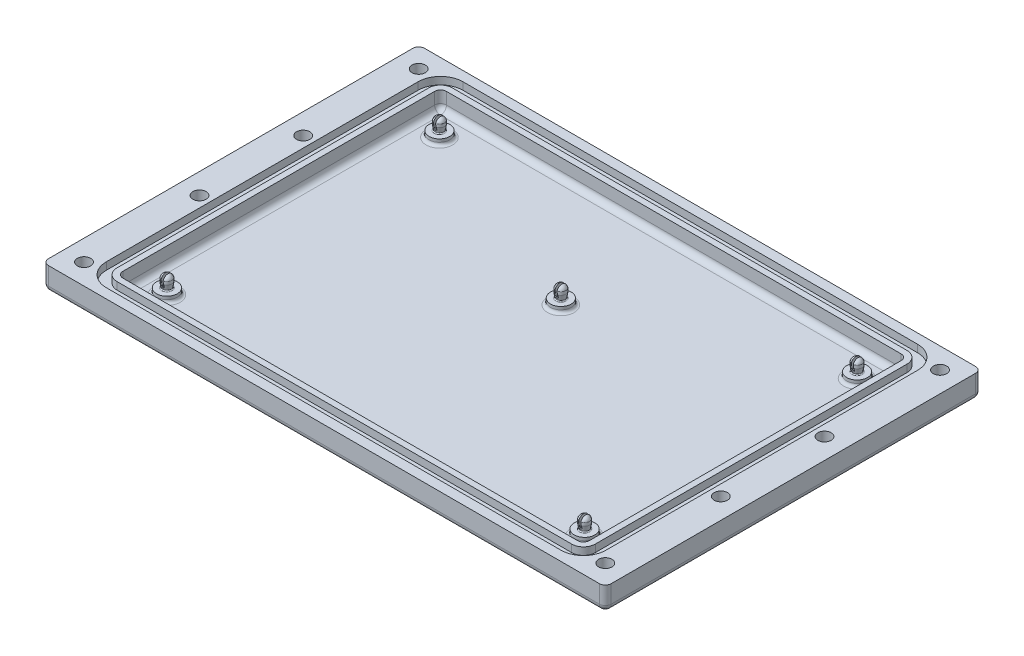
SolidWorks part; units mm, degrees
ref_plane "Front Plane" through (0, 0, 0) normal (0, 0, 1) x (1, 0, 0)
ref_plane "Top Plane" through (0, 0, 0) normal (0, 1, 0) x (1, 0, 0)
ref_plane "Right Plane" through (0, 0, 0) normal (1, 0, 0) x (0, 0, -1)
sketch "Sketch1" plane through (0, 0, 0) normal (0, 1, 0) x (1, 0, 0)
  line L1 (0, 0) -> (190, 0)
  line L2 (0, 0) -> (0, 127)
  line L3 (0, 127) -> (190, 127)
  line L4 (190, 0) -> (190, 127)
  dimension "D1" = 127
  dimension "D2" = 190
extrude "Boss-Extrude1" add sketch "Sketch1" along normal blind 8
fillet "Fillet1" radius 2 8 edges at (190, 0, -63.5) (95, 0, 0) (0, 0, -63.5) (95, 0, -127) (190, 4, -127) (0, 4, -127) (190, 4, 0) (0, 4, 0)
sketch "Sketch2" plane through (0, 8, 0) normal (0, 1, 0) x (1, 0, 0)
  line L0 (95, 127) -> (95, 0) construction
  line L1 (16.26, 8.89) -> (173.74, 8.89)
  line L2 (16.26, 8.89) -> (16.26, 118.11)
  line L3 (16.26, 118.11) -> (173.74, 118.11)
  line L4 (173.74, 8.89) -> (173.74, 118.11)
  line L5 (16.26, 8.89) -> (173.74, 118.11) construction
  line L6 (16.26, 118.11) -> (173.74, 8.89) construction
  line L7 (188, 127) -> (2, 127) construction
  line L8 (2, 0) -> (188, 0) construction
  point P0 (95, 63.5)
  point P11 (95, 63.5)
  dimension "D1" = 109.22
  dimension "D2" = 157.48
extrude "Cut-Extrude1" cut sketch "Sketch2" against normal blind 6
fillet "Fillet2" radius 2 8 edges at (95, 2, -118.11) (173.74, 2, -63.5) (95, 2, -8.89) (16.26, 2, -63.5) (16.26, 5, -8.89) (173.74, 5, -8.89) (173.74, 5, -118.11) (16.26, 5, -118.11)
sketch "Sketch3" plane through (0, 8, 0) normal (0, 1, 0) x (1, 0, 0)
  line L0 (18.26, 5.39) -> (171.74, 5.39) construction
  line L1 (177.24, 10.89) -> (177.24, 116.11) construction
  line L2 (171.74, 121.61) -> (18.26, 121.61) construction
  line L3 (12.76, 116.11) -> (12.76, 10.89) construction
  line L4 (171.74, 123.71) -> (18.26, 123.71)
  line L5 (10.66, 116.11) -> (10.66, 10.89)
  line L6 (18.26, 3.29) -> (171.74, 3.29)
  line L7 (179.34, 10.89) -> (179.34, 116.11)
  line L8 (175.74, 10.89) -> (175.74, 116.11)
  line L9 (18.26, 6.89) -> (171.74, 6.89)
  line L10 (14.26, 116.11) -> (14.26, 10.89)
  line L11 (171.74, 120.11) -> (18.26, 120.11)
  line L12 (175.74, 10.89) -> (175.74, 116.11)
  line L13 (18.26, 6.89) -> (171.74, 6.89)
  line L14 (14.26, 116.11) -> (14.26, 10.89)
  line L15 (171.74, 120.11) -> (18.26, 120.11)
  arc A0 (171.74, 5.39) -> (177.24, 10.89) centre (171.74, 10.89) ccw construction
  arc A1 (177.24, 116.11) -> (171.74, 121.61) centre (171.74, 116.11) ccw construction
  arc A2 (18.26, 121.61) -> (12.76, 116.11) centre (18.26, 116.11) ccw construction
  arc A3 (12.76, 10.89) -> (18.26, 5.39) centre (18.26, 10.89) ccw construction
  arc A4 (18.26, 123.71) -> (10.66, 116.11) centre (18.26, 116.11) ccw
  arc A5 (10.66, 10.89) -> (18.26, 3.29) centre (18.26, 10.89) ccw
  arc A6 (171.74, 3.29) -> (179.34, 10.89) centre (171.74, 10.89) ccw
  arc A7 (179.34, 116.11) -> (171.74, 123.71) centre (171.74, 116.11) ccw
  arc A8 (175.74, 116.11) -> (171.74, 120.11) centre (171.74, 116.11) ccw
  arc A9 (171.74, 6.89) -> (175.74, 10.89) centre (171.74, 10.89) ccw
  arc A10 (14.26, 10.89) -> (18.26, 6.89) centre (18.26, 10.89) ccw
  arc A11 (18.26, 120.11) -> (14.26, 116.11) centre (18.26, 116.11) ccw
  arc A12 (175.74, 116.11) -> (171.74, 120.11) centre (171.74, 116.11) ccw
  arc A13 (171.74, 6.89) -> (175.74, 10.89) centre (171.74, 10.89) ccw
  arc A14 (14.26, 10.89) -> (18.26, 6.89) centre (18.26, 10.89) ccw
  arc A15 (18.26, 120.11) -> (14.26, 116.11) centre (18.26, 116.11) ccw
  dimension "D1" = 2
  dimension "D2" = 3.6
  dimension "D3" = 1.5
extrude "Cut-Extrude2" cut sketch "Sketch3" against normal blind 2.5
sketch "Sketch4" plane through (0, 2, 0) normal (0, 1, 0) x (1, 0, 0)
  circle A0 centre (24.5, 109.5) radius 3.5
  circle A1 centre (94, 81) radius 3.5
  circle A2 centre (165.5, 109.5) radius 3.5
  circle A3 centre (165.5, 17.5) radius 3.5
  circle A4 centre (24.5, 17.5) radius 3.5
  circle A5 centre (24.5, 109.5) radius 1.6 construction
  dimension "D1" = 7
extrude "Boss-Extrude2" add sketch "Sketch4" along normal blind 2
fillet "Fillet3" radius 1 5 edges at (165.5, 2, -113) (165.5, 2, -21) (24.5, 2, -21) (94, 2, -84.5) (24.5, 2, -113)
sketch "Sketch7" plane through (0, 4, 0) normal (0, 1, 0) x (1, 0, 0)
  circle A0 centre (24.5, 109.5) radius 1.4
  circle A1 centre (94, 81) radius 1.4
  circle A2 centre (165.5, 109.5) radius 1.4
  circle A3 centre (165.5, 17.5) radius 1.4
  circle A4 centre (24.5, 17.5) radius 1.4
  dimension "D1" = 2.8
extrude "Boss-Extrude3" add sketch "Sketch7" along normal blind 2 draft 9 draft outward yes
sketch "Sketch8" plane through (0, 6, 0) normal (0, 1, 0) x (1, 0, 0)
  circle A0 centre (165.5, 109.5) radius 1.7168 construction
  circle A1 centre (94, 81) radius 1.7168 construction
  circle A2 centre (24.5, 109.5) radius 1.7168 construction
  circle A3 centre (24.5, 17.5) radius 1.7168 construction
  circle A4 centre (165.5, 17.5) radius 1.7168 construction
  circle A5 centre (165.5, 109.5) radius 1.7168
  circle A6 centre (94, 81) radius 1.7168
  circle A7 centre (24.5, 109.5) radius 1.7168
  circle A8 centre (24.5, 17.5) radius 1.7168
  circle A9 centre (165.5, 17.5) radius 1.7168
extrude "Boss-Extrude4" add sketch "Sketch8" along normal blind 1 draft 3
dome "Dome2" faces to dome 1 distance 1.3 reverse direction no elliptical dome no face at (165.5, 7, -15.8356) parameters "D1"=1.3
dome "Dome3" faces to dome 1 distance 1.3 reverse direction no elliptical dome no face at (165.5, 7, -107.8356) parameters "D1"=1.3
dome "Dome4" faces to dome 1 distance 1.3 reverse direction no elliptical dome no face at (94, 7, -79.3356) parameters "D1"=1.3
dome "Dome5" faces to dome 1 distance 1.3 reverse direction no elliptical dome no face at (24.5, 7, -15.8356) parameters "D1"=1.3
dome "Dome6" faces to dome 1 distance 1.3 reverse direction no elliptical dome no face at (24.5, 7, -107.8356) parameters "D1"=1.3
sketch "Sketch9" plane through (0, 8, 0) normal (0, 1, 0) x (1, 0, 0)
  line L1 (165.85, 14.5) -> (165.15, 14.5)
  line L2 (165.85, 14.5) -> (165.85, 20.5)
  line L3 (165.85, 20.5) -> (165.15, 20.5)
  line L4 (165.15, 14.5) -> (165.15, 20.5)
  line L5 (165.85, 14.5) -> (165.15, 20.5) construction
  line L6 (165.85, 20.5) -> (165.15, 14.5) construction
  line L7 (165.85, 106.5) -> (165.15, 106.5)
  line L8 (165.85, 106.5) -> (165.85, 112.5)
  line L9 (165.85, 112.5) -> (165.15, 112.5)
  line L10 (165.15, 106.5) -> (165.15, 112.5)
  line L11 (165.85, 106.5) -> (165.15, 112.5) construction
  line L12 (165.85, 112.5) -> (165.15, 106.5) construction
  line L13 (94.35, 78) -> (93.65, 78)
  line L14 (94.35, 78) -> (94.35, 84)
  line L15 (94.35, 84) -> (93.65, 84)
  line L16 (93.65, 78) -> (93.65, 84)
  line L17 (94.35, 78) -> (93.65, 84) construction
  line L18 (94.35, 84) -> (93.65, 78) construction
  line L19 (24.85, 106.5) -> (24.15, 106.5)
  line L20 (24.85, 106.5) -> (24.85, 112.5)
  line L21 (24.85, 112.5) -> (24.15, 112.5)
  line L22 (24.15, 106.5) -> (24.15, 112.5)
  line L23 (24.85, 106.5) -> (24.15, 112.5) construction
  line L24 (24.85, 112.5) -> (24.15, 106.5) construction
  line L25 (24.85, 14.5) -> (24.15, 14.5)
  line L26 (24.85, 14.5) -> (24.85, 20.5)
  line L27 (24.85, 20.5) -> (24.15, 20.5)
  line L28 (24.15, 14.5) -> (24.15, 20.5)
  line L29 (24.85, 14.5) -> (24.15, 20.5) construction
  line L30 (24.85, 20.5) -> (24.15, 14.5) construction
  point P0 (165.5, 17.5)
  point P6 (165.5, 109.5)
  point P12 (94, 81)
  point P18 (24.5, 109.5)
  point P24 (24.5, 17.5)
  dimension "D1" = 6
  dimension "D2" = 0.7
extrude "Cut-Extrude3" cut sketch "Sketch9" against normal offset from surface 1 and the other way through all up to face at (24.5, 4, -14)
fillet "Fillet4" radius 0.2 40 edges at (165.85, 5, -17.5) (165.5, 5, -15.9416) (165.15, 5, -17.5) (165.5, 5, -19.0584) (165.85, 5, -109.5) (165.5, 5, -107.9416) (165.15, 5, -109.5) (165.5, 5, -111.0584) (94.35, 5, -81) (94, 5, -79.4416) (93.65, 5, -81) (94, 5, -82.5584) (24.85, 5, -17.5) (24.5, 5, -15.9416) (24.15, 5, -17.5) (24.5, 5, -19.0584) (24.85, 5, -109.5) (24.5, 5, -107.9416) (24.15, 5, -109.5) (24.5, 5, -111.0584)
fillet "Fillet5" radius 0.3 5 edges at (165.5, 4, -16.1) (165.5, 4, -108.1) (94, 4, -79.6) (24.5, 4, -16.1) (24.5, 4, -108.1)
sketch "Sketch10" plane through (0, 8, 0) normal (0, 1, 0) x (1, 0, 0)
  circle A0 centre (7, 120) radius 2.25 construction
  circle A1 centre (7, 81) radius 2.25 construction
  circle A2 centre (7, 46) radius 2.25 construction
  circle A3 centre (7, 7) radius 2.25 construction
  circle A4 centre (183, 7) radius 2.25 construction
  circle A5 centre (183, 46) radius 2.25 construction
  circle A6 centre (183, 81) radius 2.25 construction
  circle A7 centre (183, 120) radius 2.25 construction
  circle A8 centre (7, 120) radius 2.25
  circle A9 centre (7, 81) radius 2.25
  circle A10 centre (7, 46) radius 2.25
  circle A11 centre (7, 7) radius 2.25
  circle A12 centre (183, 7) radius 2.25
  circle A13 centre (183, 46) radius 2.25
  circle A14 centre (183, 81) radius 2.25
  circle A15 centre (183, 120) radius 2.25
extrude "Cut-Extrude4" cut sketch "Sketch10" against normal through all
sketch "Sketch11" plane through (0, 0, 0) normal (0, -1, 0) x (1, 0, 0)
  line L0 (188, -125) -> (188, -2) construction
  line L1 (186.5, -9.0207) -> (186.5, -4.9793)
  line L2 (186.5, -4.9793) -> (183, -2.9585)
  line L3 (183, -2.9585) -> (179.5, -4.9793)
  line L4 (179.5, -4.9793) -> (179.5, -9.0207)
  line L5 (179.5, -9.0207) -> (183, -11.0415)
  line L6 (183, -11.0415) -> (186.5, -9.0207)
  line L7 (2, -2) -> (2, -125) construction
  line L8 (186.5, -48.0207) -> (186.5, -43.9793)
  line L9 (186.5, -43.9793) -> (183, -41.9585)
  line L10 (183, -41.9585) -> (179.5, -43.9793)
  line L11 (179.5, -43.9793) -> (179.5, -48.0207)
  line L12 (179.5, -48.0207) -> (183, -50.0415)
  line L13 (183, -50.0415) -> (186.5, -48.0207)
  line L14 (186.5, -78.9793) -> (183, -76.9585)
  line L15 (183, -76.9585) -> (179.5, -78.9793)
  line L16 (179.5, -78.9793) -> (179.5, -83.0207)
  line L17 (179.5, -83.0207) -> (183, -85.0415)
  line L18 (183, -85.0415) -> (186.5, -83.0207)
  line L19 (186.5, -83.0207) -> (186.5, -78.9793)
  line L20 (186.5, -117.9793) -> (183, -115.9585)
  line L21 (183, -115.9585) -> (179.5, -117.9793)
  line L22 (179.5, -117.9793) -> (179.5, -122.0207)
  line L23 (179.5, -122.0207) -> (183, -124.0415)
  line L24 (183, -124.0415) -> (186.5, -122.0207)
  line L25 (186.5, -122.0207) -> (186.5, -117.9793)
  line L26 (3.5, -117.9793) -> (3.5, -122.0207)
  line L27 (3.5, -122.0207) -> (7, -124.0415)
  line L28 (7, -124.0415) -> (10.5, -122.0207)
  line L29 (10.5, -122.0207) -> (10.5, -117.9793)
  line L30 (10.5, -117.9793) -> (7, -115.9585)
  line L31 (7, -115.9585) -> (3.5, -117.9793)
  line L32 (3.5, -78.9793) -> (3.5, -83.0207)
  line L33 (3.5, -83.0207) -> (7, -85.0415)
  line L34 (7, -85.0415) -> (10.5, -83.0207)
  line L35 (10.5, -83.0207) -> (10.5, -78.9793)
  line L36 (10.5, -78.9793) -> (7, -76.9585)
  line L37 (7, -76.9585) -> (3.5, -78.9793)
  line L38 (3.5, -43.9793) -> (3.5, -48.0207)
  line L39 (3.5, -48.0207) -> (7, -50.0415)
  line L40 (7, -50.0415) -> (10.5, -48.0207)
  line L41 (10.5, -48.0207) -> (10.5, -43.9793)
  line L42 (10.5, -43.9793) -> (7, -41.9585)
  line L43 (7, -41.9585) -> (3.5, -43.9793)
  line L44 (3.5, -4.9793) -> (3.5, -9.0207)
  line L45 (3.5, -9.0207) -> (7, -11.0415)
  line L46 (7, -11.0415) -> (10.5, -9.0207)
  line L47 (10.5, -9.0207) -> (10.5, -4.9793)
  line L48 (10.5, -4.9793) -> (7, -2.9585)
  line L49 (7, -2.9585) -> (3.5, -4.9793)
  circle A0 centre (183, -7) radius 3.5 construction
  circle A1 centre (183, -46) radius 3.5 construction
  circle A2 centre (183, -81) radius 3.5 construction
  circle A3 centre (183, -120) radius 3.5 construction
  circle A4 centre (7, -120) radius 3.5 construction
  circle A5 centre (7, -81) radius 3.5 construction
  circle A6 centre (7, -46) radius 3.5 construction
  circle A7 centre (7, -7) radius 3.5 construction
  dimension "D1" = 7
  dimension "D2" = 7
extrude "Cut-Extrude5" cut sketch "Sketch11" against normal blind 3.2
